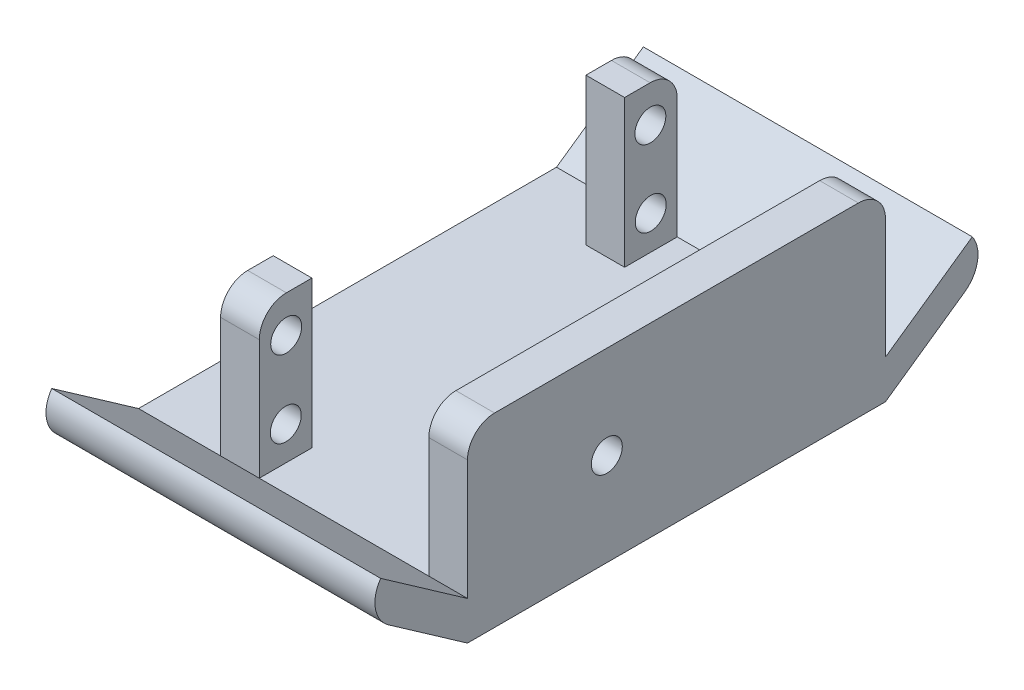
SolidWorks part; units mm, degrees
ref_plane "Front Plane" through (0, 0, 0) normal (0, 0, 1) x (1, 0, 0)
ref_plane "Top Plane" through (0, 0, 0) normal (0, 1, 0) x (1, 0, 0)
ref_plane "Right Plane" through (0, 0, 0) normal (1, 0, 0) x (0, 0, -1)
sketch "Sketch of Servo Motor" plane through (0, 0, 0) normal (0, 1, 0) x (1, 0, 0)
  line L0 (0, 0) -> (26.9, 0) construction
  line L1 (26.9, 0) -> (26.9, -40.4) construction
  line L2 (26.9, -40.4) -> (0, -40.4) construction
  line L3 (0, -40.4) -> (0, -47.2) construction
  line L4 (0, -47.2) -> (-3, -47.2) construction
  line L5 (-3, -47.2) -> (-3, -40.4) construction
  line L6 (-3, -40.4) -> (-10.6, -40.4) construction
  line L7 (-10.6, -40.4) -> (-10.6, 0) construction
  line L8 (-10.6, 0) -> (-3, 0) construction
  line L9 (-3, 0) -> (-3, 6.8) construction
  line L10 (-3, 6.8) -> (0, 6.8) construction
  line L11 (0, 6.8) -> (0, 0) construction
  line L13 (31.9, -47.2) -> (-10.6, -47.2)
  line L14 (31.9, -47.2) -> (31.9, 6.8)
  line L15 (31.9, 6.8) -> (-10.6, 6.8)
  line L16 (-10.6, -47.2) -> (-10.6, 6.8)
  dimension "D1" = 37.5
  dimension "D2" = 26.9
  dimension "D3" = 54
  dimension "D4" = 40.4
  dimension "D5" = 3
  dimension "D6" = 5
extrude "Extrude Base of Foot" add sketch "Sketch of Servo Motor" against normal blind 5
sketch "Positions of Foot Sides" plane through (0, 0, 0) normal (0, 1, 0) x (1, 0, 0)
  line L0 (-10.6, 0) -> (-3, 0) construction
  line L1 (-10.6, 6.8) -> (-10.6, -47.2) construction
  line L2 (-3, 0) -> (-3, 6.8) construction
  line L3 (31.9, 6.8) -> (-10.6, 6.8) construction
  line L4 (-3, 6.8) -> (0, 6.8) construction
  line L5 (0, 6.8) -> (0, 0) construction
  line L6 (0, 0) -> (26.9, 0) construction
  line L7 (26.9, 0) -> (26.9, -40.4) construction
  line L8 (26.9, -40.4) -> (0, -40.4) construction
  line L9 (0, -40.4) -> (0, -47.2) construction
  line L10 (-10.6, -47.2) -> (31.9, -47.2) construction
  line L11 (0, -47.2) -> (-3, -47.2) construction
  line L12 (-3, -47.2) -> (-3, -40.4) construction
  line L13 (-3, -40.4) -> (-10.6, -40.4) construction
  line L14 (-10.6, -40.4) -> (-10.6, 0) construction
  line L15 (31.9, -47.2) -> (31.9, 6.8) construction
  line L17 (31.9, 6.8) -> (26.9, 6.8)
  line L18 (31.9, 6.8) -> (31.9, -47.2)
  line L19 (31.9, -47.2) -> (26.9, -47.2)
  line L20 (26.9, 6.8) -> (26.9, -47.2)
  line L21 (0, 0) -> (5, 0)
  line L22 (0, 0) -> (0, 6.8)
  line L23 (0, 6.8) -> (5, 6.8)
  line L24 (5, 0) -> (5, 6.8)
  line L25 (0, -40.4) -> (5, -40.4)
  line L26 (0, -40.4) -> (0, -47.2)
  line L27 (0, -47.2) -> (5, -47.2)
  line L28 (5, -40.4) -> (5, -47.2)
  dimension "D1" = 3
  dimension "D2" = 5
  dimension "D3" = 5
  dimension "D4" = 26.9
extrude "Extrude Sides of Foot" add sketch "Positions of Foot Sides" along normal blind 19
fillet "Fillet Top Edges of Sides of Foot" radius 3.5 4 edges at (29.4, 19, -6.8) (2.5, 19, -6.8) (2.5, 19, 47.2) (29.4, 19, 47.2)
ref_plane "Inside RT Foot Plane" through (-10.6, 0, 0) normal (-1, 0, 0) x (0, 0, 1)
sketch "Front and Back Foot Lips" plane through (-10.6, 0, 0) normal (-1, 0, 0) x (0, 0, 1)
  line L0 (20.2, -5) -> (20.2, 19) construction
  line L1 (-6.8, -5) -> (47.2, -5) construction
  line L2 (-3.3, 19) -> (43.7, 19) construction
  line L3 (47.2, -5) -> (60.7674, 4.5) construction
  line L6 (47.2, -5) -> (47.2, 15.5) construction
  line L7 (60.7674, 4.5) -> (58.4182, 7.8551)
  line L8 (58.4182, 7.8551) -> (47.2, 0)
  line L9 (-6.8, 0) -> (47.2, 0) construction
  line L10 (47.2, 0) -> (47.2, -5)
  line L11 (47.2, -5) -> (60.7674, 4.5)
  line L12 (-6.8, 0) -> (-6.8, -5)
  line L13 (-18.0182, 7.8551) -> (-6.8, 0)
  line L14 (-20.3674, 4.5) -> (-18.0182, 7.8551)
  line L15 (-6.8, -5) -> (-20.3674, 4.5)
  dimension "D1" = 55
  dimension "D2" = 9.5
  dimension "D3" = 90
  dimension "D4" = 270
extrude "Extrude Foot Lips" add sketch "Front and Back Foot Lips" against normal through all
fillet "Fillet Foot Lips" radius 4.1 2 edges at (10.65, 4.5, 60.7674) (10.65, 4.5, -20.3674)
ref_plane "Top Servo Motor Screw Holes Plane" through (0, 0, 0) normal (-1, 0, 0) x (0, 0, 1)
sketch "Hole Dimensions for M4 Bolt" plane through (0, 0, 0) normal (-1, 0, 0) x (0, 0, 1)
  line L0 (0, 9.5) -> (49.8704, 9.5) construction
  line L2 (0, 19) -> (0, 0) construction
  line L3 (49.8704, 9.5) -> (-9.3392, 9.5) construction
  line L4 (-3.4, 0) -> (-3.3, 19) construction
  line L5 (-6.8, 0) -> (0, 0) construction
  line L6 (43.8, 0) -> (43.7, 19) construction
  line L7 (40.4, 0) -> (47.2, 0) construction
  circle A0 centre (-3.325, 14.2589) radius 2
  circle A1 centre (-3.3771, 4.3589) radius 2
  circle A2 centre (43.725, 14.2589) radius 2
  circle A3 centre (43.7771, 4.3589) radius 2
  dimension "D2" = 4
  dimension "D1" = 9.9
extrude "Extrude Cut Hole for M4 Bolt" cut sketch "Hole Dimensions for M4 Bolt" against normal blind 5
ref_plane "Outside Foot Plane" through (31.9, 0, 0) normal (1, 0, 0) x (0, 0, -1)
sketch "Dimensions for Outside Foot M4 Hole" plane through (31.9, 0, 0) normal (1, 0, 0) x (0, 0, -1)
  line L0 (-20.2, -5) -> (-20.2, 19) construction
  line L1 (-47.2, -5) -> (6.8, -5) construction
  line L2 (-43.7, 19) -> (3.3, 19) construction
  line L3 (-20.2, 7) -> (-47.2, 7) construction
  line L4 (-47.2, 0) -> (-47.2, 15.5) construction
  circle A0 centre (-29.2, 7) radius 2
  dimension "D1" = 4
  dimension "D2" = 18
extrude "Cut-Extrude1" cut sketch "Dimensions for Outside Foot M4 Hole" against normal up to next
